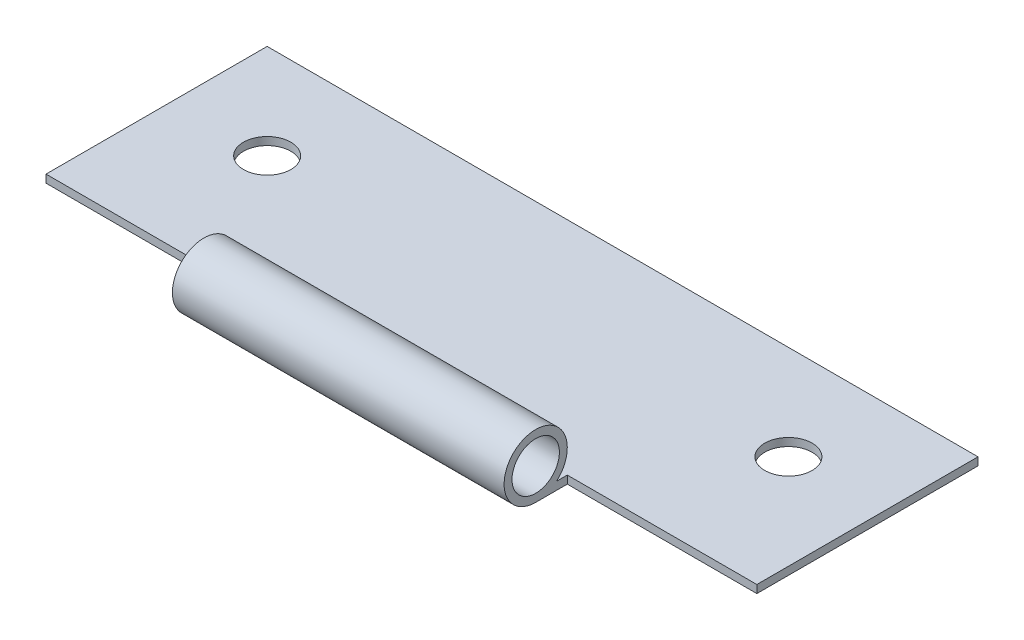
SolidWorks part; units mm, degrees
material "Latón"
ref_plane "Alzado" through (0, 0, 0) normal (0, 0, 1) x (1, 0, 0)
ref_plane "Planta" through (0, 0, 0) normal (0, 1, 0) x (1, 0, 0)
ref_plane "Vista lateral" through (0, 0, 0) normal (1, 0, 0) x (0, 0, -1)
sketch "Croquis1" plane through (0, 0, 0) normal (0, 1, 0) x (1, 0, 0)
  line L0 (22.5, 16) -> (22.5, 7.7131) construction
  line L1 (0, 0) -> (45, 0)
  line L2 (0, 0) -> (0, 16)
  line L3 (0, 16) -> (45, 16)
  line L4 (45, 0) -> (45, 16)
  circle A0 centre (6, 10) radius 1.5
  circle A1 centre (39, 10) radius 1.5
  dimension "D3" = 3
  dimension "D1" = 45
  dimension "D2" = 16
  dimension "D4" = 6
  dimension "D5" = 6
extrude "Saliente-Extruir1" add sketch "Croquis1" along normal blind 0.5
sketch "Croquis2" plane through (45, 0, 0) normal (1, 0, 0) x (0, 0, -1)
  circle A0 centre (0, 2) radius 2
  circle A1 centre (0, 2) radius 1.5
  dimension "D1" = 4
extrude "Saliente-Extruir2" add sketch "Croquis2" against normal up to surface (45 mm away) up to face at (0, 0.25, -8)
sketch "Croquis3" plane through (0, 0, 0) normal (0, -1, 0) x (1, 0, 0)
  line L1 (0, -2) -> (45, -2) construction
  line L2 (33, -2) -> (45, -2)
  line L3 (33, -2) -> (33, 2)
  line L4 (33, 2) -> (45, 2)
  line L6 (45, -2) -> (45, 2)
  line L7 (45, 2) -> (0, 2) construction
  line L9 (12, 2) -> (0, 2)
  line L10 (12, 2) -> (12, -2)
  line L11 (12, -2) -> (0, -2)
  line L12 (0, 2) -> (0, -2)
  line L13 (0, -16) -> (0, -1.3229) construction
  dimension "D1" = 21
extrude "Cortar-Extruir1" cut sketch "Croquis3" against normal through all
